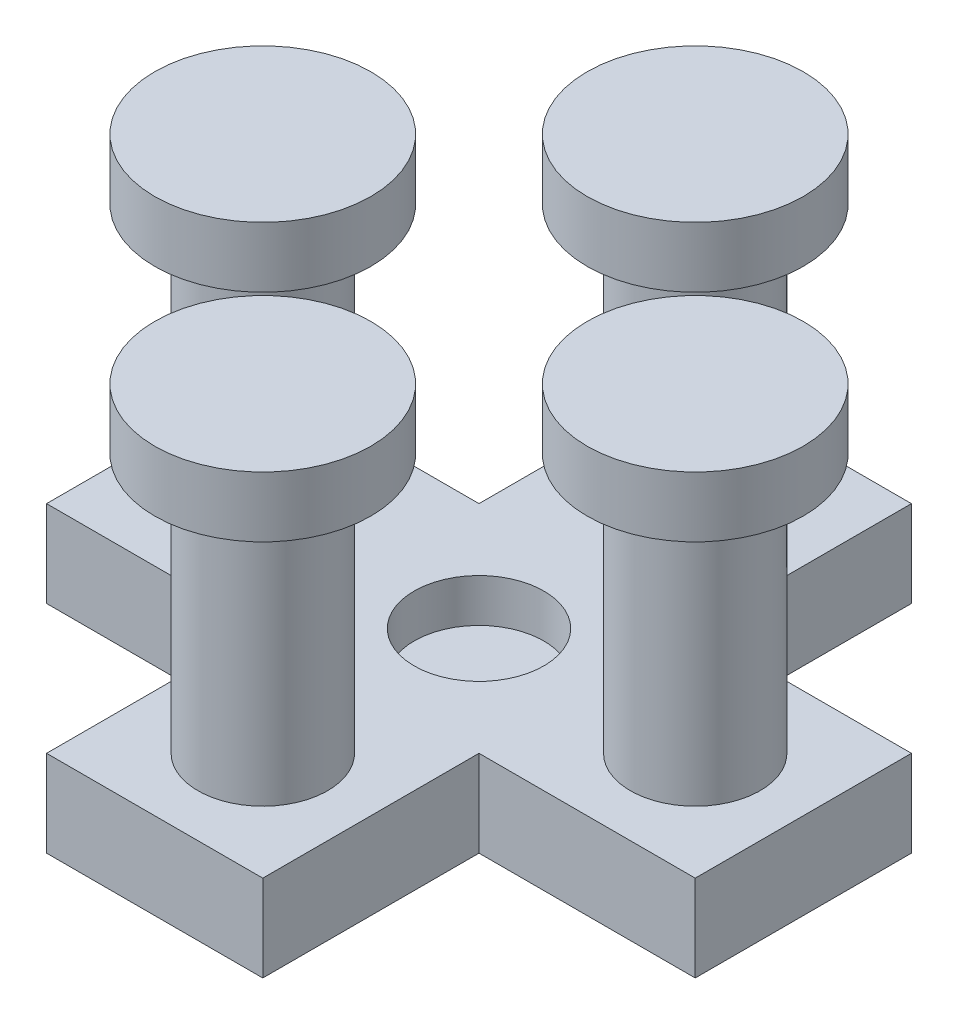
SolidWorks part; units mm, degrees
ref_plane "Front Plane" through (0, 0, 0) normal (0, 0, 1) x (1, 0, 0)
ref_plane "Top Plane" through (0, 0, 0) normal (0, 1, 0) x (1, 0, 0)
ref_plane "Right Plane" through (0, 0, 0) normal (1, 0, 0) x (0, 0, -1)
sketch "Sketch1" plane through (0, 0, 0) normal (0, 1, 0) x (1, 0, 0)
  line L0 (-8.3487, -10.4521) -> (-8.3487, -4.1021)
  line L1 (-8.3487, -4.1021) -> (-1.9987, -4.1021)
  line L2 (-1.9987, -4.1021) -> (-1.9987, -10.4521)
  line L3 (-1.9987, -10.4521) -> (4.3513, -10.4521)
  line L4 (4.3513, -10.4521) -> (4.3513, -16.8021)
  line L5 (4.3513, -16.8021) -> (-1.9987, -16.8021)
  line L6 (-1.9987, -16.8021) -> (-1.9987, -23.1521)
  line L7 (-1.9987, -23.1521) -> (-8.3487, -23.1521)
  line L8 (-8.3487, -23.1521) -> (-8.3487, -16.8021)
  line L9 (-8.3487, -16.8021) -> (-14.6987, -16.8021)
  line L10 (-14.6987, -16.8021) -> (-14.6987, -10.4521)
  line L11 (-14.6987, -10.4521) -> (-8.3487, -10.4521)
  dimension "D1" = 6.35
  dimension "D2" = 6.35
  dimension "D3" = 6.35
  dimension "D4" = 6.35
  dimension "D5" = 6.35
  dimension "D6" = 6.35
  dimension "D7" = 6.35
  dimension "D8" = 6.35
  dimension "D9" = 6.35
  dimension "D10" = 6.35
extrude "body" add sketch "Sketch1" along normal blind 2.54
sketch "Sketch2" plane through (0, 2.54, 0) normal (0, 1, 0) x (1, 0, 0)
  line L0 (-8.3487, -10.4521) -> (-14.6987, -10.4521) construction
  line L1 (-1.9987, -23.1521) -> (-1.9987, -16.8021) construction
  line L2 (-1.9987, -16.8021) -> (4.3513, -16.8021) construction
  line L3 (-1.9987, -10.4521) -> (-1.9987, -4.1021) construction
  line L4 (-1.9987, -4.1021) -> (-8.3487, -4.1021) construction
  line L5 (-14.6987, -10.4521) -> (-14.6987, -16.8021) construction
  line L6 (-8.3487, -23.1521) -> (-1.9987, -23.1521) construction
  line L7 (4.3513, -16.8021) -> (4.3513, -10.4521) construction
  circle A0 centre (-5.1737, -7.2771) radius 1.905
  circle A1 centre (1.1763, -13.6271) radius 1.905
  circle A2 centre (-5.1737, -19.9771) radius 1.905
  circle A3 centre (-11.5237, -13.6271) radius 1.905
  dimension "D1" = 3.81
  dimension "D2" = 3.81
  dimension "D3" = 3.81
  dimension "D4" = 3.81
  dimension "D5" = 3.175
  dimension "D6" = 3.175
  dimension "D7" = 3.175
  dimension "D8" = 3.175
  dimension "D9" = 3.175
  dimension "D10" = 3.175
  dimension "D11" = 3.175
  dimension "D12" = 3.175
extrude "flag" add sketch "Sketch2" along normal blind 7.62
ref_point "centre 1"
ref_point "centre 2"
ref_point "centre 3"
ref_point "centre 4"
ref_plane "plane o' feet" through (0, 10.16, 0) normal (0, 1, 0) x (1, 0, 0)
sketch "Sketch3" plane through (0, 10.16, 0) normal (0, 1, 0) x (1, 0, 0)
  circle A0 centre (-5.1737, -7.2771) radius 3.175
  circle A1 centre (-11.5237, -13.6271) radius 3.175
  circle A2 centre (-5.1737, -19.9771) radius 3.175
  circle A3 centre (1.1763, -13.6271) radius 3.175
  dimension "D1" = 6.35
  dimension "D2" = 6.35
  dimension "D3" = 6.35
  dimension "D4" = 6.35
extrude "feet" add sketch "Sketch3" along normal blind 1.778
sketch "Sketch4" plane through (0, 2.54, 0) normal (0, 1, 0) x (1, 0, 0)
  line L0 (-8.3487, -23.1521) -> (-1.9987, -23.1521) construction
  line L3 (-1.9987, -4.1021) -> (-8.3487, -4.1021) construction
  circle A0 centre (-5.1737, -13.6271) radius 1.905
  point P10 (-5.1737, -4.1021)
  point P14 (-5.1737, -23.1521)
  dimension "D1" = 3.81
  dimension "D2" = 9.525
  dimension "D3" = 0
extrude "spring hole" cut sketch "Sketch4" against normal blind 1.27
